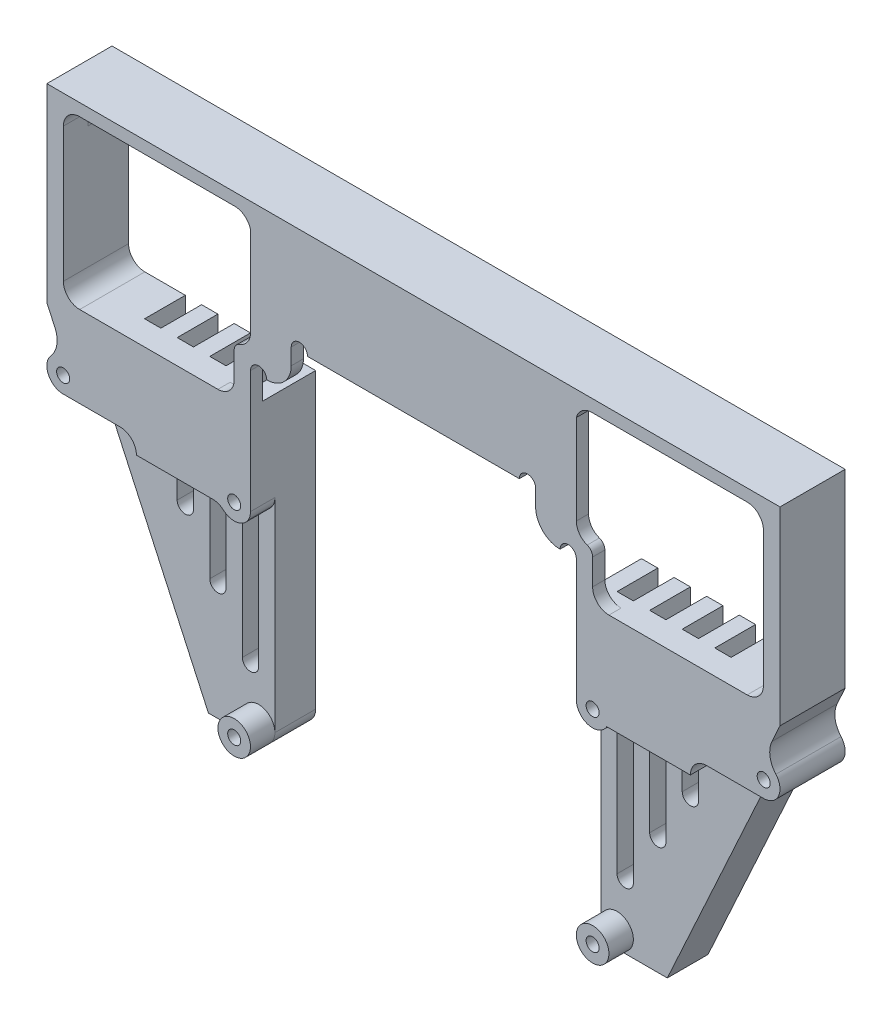
SolidWorks part; units mm, degrees
material "A2017"
ref_plane "正面" through (0, 0, 0) normal (0, 0, 1) x (1, 0, 0)
ref_plane "平面" through (0, 0, 0) normal (0, 1, 0) x (1, 0, 0)
ref_plane "右側面" through (0, 0, 0) normal (1, 0, 0) x (0, 0, -1)
sketch "ｽｹｯﾁ2" plane through (0, 0, 0) normal (0, 0, 1) x (1, 0, 0)
  line L0 (45, -77) -> (-45, -77)
  line L1 (-45, -77) -> (-45, -100.2724)
  line L2 (40.4547, -110.1895) -> (28.1283, -137.0833) construction
  line L3 (57.5, -85) -> (32.6737, -139.1665) construction
  line L4 (23.583, -145) -> (-23.583, -145) construction
  line L5 (-32.6737, -139.1665) -> (-57.5, -85) construction
  line L6 (45, -112.2727) -> (32.6737, -139.1665) construction
  line L7 (23.583, -145) -> (-23.583, -145) construction
  line L8 (-32.6737, -139.1665) -> (-45, -112.2727) construction
  line L9 (45, -77) -> (45, -100.2724)
  line L10 (45, -100.2724) -> (28.1665, -137)
  line L11 (-20, -80) -> (20, -80)
  line L12 (-28.1665, -137) -> (-45, -100.2724)
  line L13 (-28.1283, -137.0833) -> (-40.4547, -110.1895) construction
  line L15 (-20, -135) -> (-20, -80)
  line L19 (22, -137) -> (28.1665, -137)
  line L20 (-22, -137) -> (-28.1665, -137)
  line L22 (23.583, -140) -> (-23.583, -140) construction
  line L23 (20, -80) -> (20, -135.0066)
  line L24 (-43, -137) -> (-22, -137) construction
  line L25 (-20, -135) -> (-20, -79) construction
  line L26 (-45, -79) -> (-45, -135) construction
  line L27 (43, -77) -> (22, -77) construction
  line L28 (45, -135) -> (45, -79) construction
  line L29 (22, -137) -> (43, -137) construction
  line L30 (20, -79) -> (20, -135) construction
  arc A0 (23.583, -145) -> (32.6737, -139.1665) centre (23.583, -135) ccw construction
  arc A1 (-32.6737, -139.1665) -> (-23.583, -145) centre (-23.583, -135) ccw construction
  arc A2 (23.583, -145) -> (32.6737, -139.1665) centre (23.583, -135) ccw construction
  arc A3 (-32.6737, -139.1665) -> (-23.583, -145) centre (-23.583, -135) ccw construction
  arc A4 (-21.8257, -136.9924) -> (-20, -135) centre (-22, -135) ccw construction
  arc A5 (20.0076, -135.1743) -> (22, -137) centre (22, -135) ccw construction
  arc A8 (20, -135.0066) -> (22, -137) centre (22, -135) ccw
  arc A9 (-22, -137) -> (-20, -135) centre (-22, -135) ccw
  arc A10 (-28.1283, -137.0833) -> (-23.583, -140) centre (-23.583, -135) ccw construction
  arc A11 (23.583, -140) -> (28.1283, -137.0833) centre (23.583, -135) ccw construction
  dimension "D1" = 5
  dimension "D2" = 3
extrude "ﾎﾞｽ - 押し出し1" add sketch "ｽｹｯﾁ2" along normal blind 5
sketch "ｽｹｯﾁ3" plane through (0, 0, 5) normal (0, 0, 1) x (1, 0, 0)
  circle A0 centre (-43, -107) radius 2
  circle A1 centre (43, -107) radius 2
  circle A2 centre (43, -107) radius 1.25 construction
  dimension "D1" = 4
extrude "ﾎﾞｽ - 押し出し2" add sketch "ｽｹｯﾁ3" against normal up to surface (5 mm away) up to face at (0.0002, -111.1149, 0)
fillet "ﾌｨﾚｯﾄ1" radius 3 4 edges at (-42.8299, -105.0073, 2.5) (-41.3794, -108.172, 2.5) (41.3794, -108.172, 2.5) (42.8299, -105.0073, 2.5)
sketch "ｽｹｯﾁ4" plane through (0, 0, 5) normal (0, 0, 1) x (1, 0, 0)
  circle A0 centre (-43, -107) radius 2
  circle A1 centre (-22, -110) radius 2
  circle A2 centre (-22, -135) radius 2
  circle A3 centre (22, -135) radius 2
  circle A4 centre (22, -110) radius 2
  circle A5 centre (43, -107) radius 2
  dimension "D1" = 4
extrude "ﾎﾞｽ - 押し出し3" add sketch "ｽｹｯﾁ4" along normal blind 3
sketch "ｽｹｯﾁ5" plane through (0, 0, 5) normal (0, 0, 1) x (1, 0, 0)
  line L0 (20, -80) -> (20, -110) construction
  line L1 (20, -98.9998) -> (42.9701, -98.9998)
  line L2 (20, -98.9998) -> (20, -108.9998)
  line L3 (34, -108.9998) -> (42.9701, -108.9998)
  line L4 (42.9701, -98.9998) -> (42.9701, -108.9998)
  line L5 (20, -110) -> (20, -135) construction
  line L6 (20, -110.9998) -> (34, -110.9998)
  line L7 (20, -110.9998) -> (20, -108.9998)
  line L8 (0, -77) -> (0, -134.0805) construction
  line L9 (34, -110.9998) -> (34, -108.9998)
  line L10 (45, -77) -> (-45, -77) construction
  line L11 (-34, -110.9998) -> (-34, -108.9998)
  line L12 (-20, -110.9998) -> (-20, -108.9998)
  line L13 (-20, -110.9998) -> (-34, -110.9998)
  line L14 (-42.9701, -98.9998) -> (-42.9701, -108.9998)
  line L15 (-34, -108.9998) -> (-42.9701, -108.9998)
  line L16 (-20, -98.9998) -> (-20, -108.9998)
  line L17 (-20, -98.9998) -> (-42.9701, -98.9998)
  circle A0 centre (43, -107) radius 2 construction
  arc A1 (42.9701, -108.9998) -> (40.198, -110.7495) centre (42.9252, -111.9994) ccw construction
  dimension "D1" = 10
  dimension "D2" = 14
  dimension "D3" = 2
extrude "ﾎﾞｽ - 押し出し4" add sketch "ｽｹｯﾁ5" along normal up to surface (3 mm away) up to face at (24, -110, 8)
sketch "ｽｹｯﾁ6" plane through (0, 0, 8) normal (0, 0, 1) x (1, 0, 0)
  line L0 (0, -77) -> (0, -111.4657) construction
  line L1 (42.9701, -98.9998) -> (37.9701, -98.9998)
  line L2 (42.9701, -98.9998) -> (42.9701, -103.9998)
  line L3 (42.9701, -103.9998) -> (37.9701, -103.9998)
  line L4 (37.9701, -98.9998) -> (37.9701, -103.9998)
  line L5 (45, -77) -> (-45, -77) construction
  line L6 (-37.9701, -98.9998) -> (-37.9701, -103.9998)
  line L7 (-42.9701, -103.9998) -> (-37.9701, -103.9998)
  line L8 (-42.9701, -98.9998) -> (-42.9701, -103.9998)
  line L9 (-42.9701, -98.9998) -> (-37.9701, -98.9998)
  dimension "D1" = 5
  dimension "D2" = 5
extrude "ｶｯﾄ - 押し出し1" cut sketch "ｽｹｯﾁ6" against normal up to surface (3 mm away) up to face at (20.3913, -135.9447, 5)
sketch "ｽｹｯﾁ7" plane through (0, 0, 5) normal (0, 0, 1) x (1, 0, 0)
  line L0 (45, -100.2724) -> (45, -77) construction
  line L1 (44.0112, -102.4297) -> (45, -100.2724) construction
  line L2 (45, -100.2724) -> (45, -77)
  line L3 (44.0112, -102.4297) -> (45, -100.2724)
  line L4 (-45, -77) -> (-45, -100.2724) construction
  line L5 (-45, -100.2724) -> (-44.0112, -102.4297) construction
  line L6 (-45, -77) -> (-45, -100.2724)
  line L7 (-45, -100.2724) -> (-44.0112, -102.4297)
  line L8 (45, -77) -> (-45, -77) construction
  line L9 (45, -77) -> (-45, -77)
  line L10 (42.9701, -105.0002) -> (42.9701, -80)
  line L11 (42.9701, -80) -> (-42.9701, -80)
  line L12 (-42.9701, -80) -> (-42.9701, -105.0002)
  arc A0 (44.0112, -102.4297) -> (44.4954, -105.6719) centre (46.7384, -103.6797) ccw construction
  arc A1 (44.0112, -102.4297) -> (44.4954, -105.6719) centre (46.7384, -103.6797) ccw
  arc A2 (-44.4954, -105.6719) -> (-44.0112, -102.4297) centre (-46.7384, -103.6797) ccw construction
  arc A3 (-44.4954, -105.6719) -> (-44.0112, -102.4297) centre (-46.7384, -103.6797) ccw
  arc A5 (42.9701, -108.9998) -> (42.9701, -105.0002) centre (43, -107) ccw construction
  arc A6 (-42.9701, -105.0002) -> (-44.4954, -105.6719) centre (-43, -107) ccw construction
  arc A8 (44.4954, -105.6719) -> (42.9701, -105.0002) centre (43, -107) ccw
  arc A9 (-42.9701, -105.0002) -> (-44.4954, -105.6719) centre (-43, -107) ccw
extrude "ﾎﾞｽ - 押し出し5" add sketch "ｽｹｯﾁ7" along normal up to surface (3 mm away) up to face at (32.6255, -106.7271, 8)
sketch "ｽｹｯﾁ8" plane through (0, 0, 5) normal (0, 0, 1) x (1, 0, 0)
  line L0 (42.9701, -103.9998) -> (42.9701, -80) construction
  line L1 (42.9701, -80) -> (20, -80) construction
  line L2 (20, -80) -> (20, -98.9998) construction
  line L3 (20, -98.9998) -> (37.9701, -98.9998) construction
  line L4 (37.9701, -98.9998) -> (37.9701, -103.9998) construction
  line L5 (37.9701, -103.9998) -> (42.9701, -103.9998) construction
  line L6 (-20, -80) -> (-42.9701, -80) construction
  line L7 (-42.9701, -80) -> (-42.9701, -103.9998) construction
  line L8 (-42.9701, -103.9998) -> (-37.9701, -103.9998) construction
  line L9 (-37.9701, -103.9998) -> (-37.9701, -98.9998) construction
  line L10 (-37.9701, -98.9998) -> (-20, -98.9998) construction
  line L11 (-20, -98.9998) -> (-20, -80) construction
  line L12 (42.9701, -103.9998) -> (42.9701, -80)
  line L13 (42.9701, -80) -> (20, -80)
  line L14 (20, -80) -> (20, -98.9998)
  line L15 (20, -98.9998) -> (37.9701, -98.9998)
  line L16 (37.9701, -98.9998) -> (37.9701, -103.9998)
  line L17 (37.9701, -103.9998) -> (42.9701, -103.9998)
  line L18 (-20, -80) -> (-42.9701, -80)
  line L19 (-42.9701, -80) -> (-42.9701, -103.9998)
  line L20 (-42.9701, -103.9998) -> (-37.9701, -103.9998)
  line L21 (-37.9701, -103.9998) -> (-37.9701, -98.9998)
  line L22 (-37.9701, -98.9998) -> (-20, -98.9998)
  line L23 (-20, -98.9998) -> (-20, -80)
extrude "ｶｯﾄ - 押し出し2" cut sketch "ｽｹｯﾁ8" against normal through all
fillet "ﾌｨﾚｯﾄ2" radius 2 6 edges at (-42.9701, -103.9998, 4) (-37.9701, -103.9998, 4) (37.9701, -103.9998, 4) (42.9701, -103.9998, 4) (42.9701, -80, 4) (-42.9701, -80, 4)
sketch "ｽｹｯﾁ9" plane through (0, 0, 8) normal (0, 0, 1) x (1, 0, 0)
  line L0 (20, -77) -> (20, -82.5) construction
  line L1 (42.9701, -82) -> (20, -82)
  line L2 (42.9701, -82) -> (42.9701, -78.5)
  line L3 (42.9701, -78.5) -> (20, -78.5)
  line L4 (20, -82) -> (20, -78.5)
  line L5 (45, -77) -> (-45, -77) construction
  line L6 (0, -77) -> (0, -137.6393) construction
  line L7 (-20, -82) -> (-20, -78.5)
  line L8 (-42.9701, -78.5) -> (-20, -78.5)
  line L9 (-42.9701, -82) -> (-42.9701, -78.5)
  line L10 (-42.9701, -82) -> (-20, -82)
  dimension "D1" = 1.5
extrude "ｶｯﾄ - 押し出し3" cut sketch "ｽｹｯﾁ9" against normal blind 3
fillet "ﾌｨﾚｯﾄ3" radius 2 4 edges at (42.9701, -78.5, 6.5) (20, -78.5, 6.5) (-20, -78.5, 6.5) (-42.9701, -78.5, 6.5)
fillet "ﾌｨﾚｯﾄ4" radius 2 5 edges at (34, -108.9998, 6.5) (-20, -110.9998, 6.5) (20, -110.9998, 6.5) (-23.7322, -110.9998, 6.5) (-34, -108.9998, 6.5)
sketch "ｽｹｯﾁ10" plane through (0, 0, 0) normal (0, 0, -1) x (-1, 0, 0)
  line L0 (-23, -98.9998) -> (-23, -128.9998) construction
  line L1 (-20, -98.9998) -> (-37.9701, -98.9998) construction
  line L2 (-22, -98.9998) -> (-22, -128.9998)
  line L3 (-24, -98.9998) -> (-24, -128.9998)
  line L4 (-20, -98.9998) -> (-20, -135.0066) construction
  line L5 (-27, -98.9998) -> (-27, -122.6356) construction
  line L6 (-26, -98.9998) -> (-26, -122.6356)
  line L7 (-28, -98.9998) -> (-28, -122.6356)
  line L8 (-23, -128.9998) -> (-39.9701, -101.9998) construction
  line L9 (-31, -98.9998) -> (-31, -116.2715) construction
  line L10 (-30, -98.9998) -> (-30, -116.2715)
  line L11 (-32, -98.9998) -> (-32, -116.2715)
  line L12 (-35, -98.9998) -> (-35, -109.9073) construction
  line L13 (-34, -98.9998) -> (-34, -109.9073)
  line L14 (-36, -98.9998) -> (-36, -109.9073)
  line L15 (0, -77) -> (0, -136.588) construction
  line L16 (-45, -77) -> (45, -77) construction
  line L17 (23, -98.9998) -> (23, -128.9998) construction
  line L18 (22, -98.9998) -> (22, -128.9998)
  line L19 (24, -98.9998) -> (24, -128.9998)
  line L20 (27, -98.9998) -> (27, -122.6356) construction
  line L21 (26, -98.9998) -> (26, -122.6356)
  line L22 (28, -98.9998) -> (28, -122.6356)
  line L23 (31, -98.9998) -> (31, -116.2715) construction
  line L24 (30, -98.9998) -> (30, -116.2715)
  line L25 (32, -98.9998) -> (32, -116.2715)
  line L26 (35, -98.9998) -> (35, -109.9073) construction
  line L27 (34, -98.9998) -> (34, -109.9073)
  line L28 (36, -98.9998) -> (36, -109.9073)
  line L29 (23, -128.9998) -> (39.9701, -101.9998) construction
  arc A0 (-22, -98.9998) -> (-24, -98.9998) centre (-23, -98.9998) ccw
  arc A1 (-24, -128.9998) -> (-22, -128.9998) centre (-23, -128.9998) ccw
  arc A2 (-26, -98.9998) -> (-28, -98.9998) centre (-27, -98.9998) ccw
  arc A3 (-28, -122.6356) -> (-26, -122.6356) centre (-27, -122.6356) ccw
  arc A4 (-30, -98.9998) -> (-32, -98.9998) centre (-31, -98.9998) ccw
  arc A5 (-32, -116.2715) -> (-30, -116.2715) centre (-31, -116.2715) ccw
  arc A6 (-34, -98.9998) -> (-36, -98.9998) centre (-35, -98.9998) ccw
  arc A7 (-36, -109.9073) -> (-34, -109.9073) centre (-35, -109.9073) ccw
  arc A8 (22, -98.9998) -> (24, -98.9998) centre (23, -98.9998) cw
  arc A9 (24, -128.9998) -> (22, -128.9998) centre (23, -128.9998) cw
  arc A10 (26, -98.9998) -> (28, -98.9998) centre (27, -98.9998) cw
  arc A11 (28, -122.6356) -> (26, -122.6356) centre (27, -122.6356) cw
  arc A12 (30, -98.9998) -> (32, -98.9998) centre (31, -98.9998) cw
  arc A13 (32, -116.2715) -> (30, -116.2715) centre (31, -116.2715) cw
  arc A14 (34, -98.9998) -> (36, -98.9998) centre (35, -98.9998) cw
  arc A15 (36, -109.9073) -> (34, -109.9073) centre (35, -109.9073) cw
  point P4 (-23, -113.9998)
  point P13 (-27, -110.8177)
  point P23 (-31, -107.6356)
  point P30 (-35, -104.4536)
  point P42 (23, -113.9998)
  point P49 (27, -110.8177)
  point P56 (31, -107.6356)
  point P63 (35, -104.4536)
  dimension "D1" = 2
  dimension "D2" = 2
  dimension "D3" = 30
  dimension "D4" = 2
  dimension "D5" = 2
  dimension "D6" = 2
extrude "ｶｯﾄ - 押し出し4" cut sketch "ｽｹｯﾁ10" against normal blind 5
hole_wizard "M2 ねじ穴1" positions "ｽｹｯﾁ11" profile "ｽｹｯﾁ13" tap size "M2" standard "JIS" end condition through all
sketch "ｽｹｯﾁ11" plane through (0, 0, 8) normal (0, 0, 1) x (1, 0, 0)
  point P0 (43, -107)
  point P3 (22, -110)
  point P6 (22, -135)
  point P9 (-22, -110)
  point P12 (-22, -135)
  point P15 (-43, -107)
sketch "ｽｹｯﾁ13" plane through (43, -107, 8) normal (1, 0, 0) x (0, -1, 0)
  line L0 (0, 0) -> (0, 8)
  line L1 (0, 8) -> (0.8, 8)
  line L2 (0.8, 8) -> (0.8, 0)
  line L5 (0.8, 0) -> (0, 0)
  line L11 (0, -6.35) -> (0, 107.95) construction
  dimension "次ｻｰﾌｪｽまでのねじ下穴ﾄﾞﾘﾙ直径" = 1.6
  dimension "次ｻｰﾌｪｽまでのねじ下穴ﾄﾞﾘﾙの深さ" = 8
cosmetic thread "穴のねじ山1" parameters "D2"=2
cosmetic thread "穴のねじ山2" parameters "D2"=2
cosmetic thread "穴のねじ山3" parameters "D2"=2
cosmetic thread "穴のねじ山4" parameters "D2"=2
cosmetic thread "穴のねじ山5" parameters "D2"=2
cosmetic thread "穴のねじ山6" parameters "D2"=2
sketch "ｽｹｯﾁ14" plane through (0, 0, 8) normal (0, 0, 1) x (1, 0, 0)
  line L0 (-42.9701, -101.9998) -> (-42.9701, -80.5) construction
  line L1 (-40.9701, -103.9998) -> (-39.9701, -103.9998) construction
  line L2 (-37.9701, -101.9998) -> (-37.9701, -98.9998) construction
  line L3 (42.9701, -80.5) -> (42.9701, -101.9998) construction
  line L4 (39.9701, -103.9998) -> (40.9701, -103.9998) construction
  line L5 (37.9701, -98.9998) -> (37.9701, -101.9998) construction
  line L6 (-42.9701, -101.9998) -> (-42.9701, -98.9998)
  line L7 (-40.9701, -103.9998) -> (-39.9701, -103.9998)
  line L8 (-37.9701, -101.9998) -> (-37.9701, -98.9998)
  line L9 (42.9701, -98.9998) -> (42.9701, -101.9998)
  line L10 (39.9701, -103.9998) -> (40.9701, -103.9998)
  line L11 (37.9701, -98.9998) -> (37.9701, -101.9998)
  line L12 (37.9701, -98.9998) -> (42.9701, -98.9998)
  line L13 (-37.9701, -98.9998) -> (-42.9701, -98.9998)
  arc A0 (-42.9701, -101.9998) -> (-40.9701, -103.9998) centre (-40.9701, -101.9998) ccw construction
  arc A1 (-39.9701, -103.9998) -> (-37.9701, -101.9998) centre (-39.9701, -101.9998) ccw construction
  arc A2 (40.9701, -103.9998) -> (42.9701, -101.9998) centre (40.9701, -101.9998) ccw construction
  arc A3 (37.9701, -101.9998) -> (39.9701, -103.9998) centre (39.9701, -101.9998) ccw construction
  arc A4 (-42.9701, -101.9998) -> (-40.9701, -103.9998) centre (-40.9701, -101.9998) ccw
  arc A5 (-39.9701, -103.9998) -> (-37.9701, -101.9998) centre (-39.9701, -101.9998) ccw
  arc A6 (40.9701, -103.9998) -> (42.9701, -101.9998) centre (40.9701, -101.9998) ccw
  arc A7 (37.9701, -101.9998) -> (39.9701, -103.9998) centre (39.9701, -101.9998) ccw
extrude "ﾎﾞｽ - 押し出し6" add sketch "ｽｹｯﾁ14" against normal up to surface (8 mm away) up to face at (43.8, -107, 0)
fillet "ﾌｨﾚｯﾄ5" radius 2 2 edges at (-42.9701, -98.9998, 4) (42.9701, -98.9998, 4)
sketch "ｽｹｯﾁ15" plane through (0, 0, 8) normal (0, 0, 1) x (1, 0, 0)
  line L0 (-14.5, -90) -> (14.5, -90) construction
  line L1 (-20, -80) -> (20, -80)
  line L2 (-20, -80) -> (-20, -90)
  line L3 (-20, -90) -> (20, -90)
  line L4 (20, -80) -> (20, -90)
extrude "ﾎﾞｽ - 押し出し8" add sketch "ｽｹｯﾁ15" against normal blind 1.5
sketch "ｽｹｯﾁ16" plane through (0, 0, 8) normal (0, 0, 1) x (1, 0, 0)
  line L2 (20, -98.9998) -> (20, -95)
  line L3 (20, -95.5) -> (20, -93) construction
  line L4 (20, -95) -> (18, -95)
  line L5 (15, -92) -> (15, -90)
  line L6 (-20, -90) -> (20, -90) construction
  line L11 (20, -135) -> (20, -79) construction
  line L12 (20, -98.9998) -> (22, -98.9998) construction
  line L13 (20, -98.9998) -> (22, -98.9998)
  line L14 (22, -98.9998) -> (22, -93)
  line L15 (15, -90) -> (20, -90)
  line L16 (22, -93) -> (20, -93)
  line L17 (20, -93) -> (20, -90)
  arc A0 (15, -92) -> (18, -95) centre (18, -92) ccw construction
  arc A1 (15, -92) -> (18, -95) centre (18, -92) ccw
  dimension "D1" = 3
extrude "ﾎﾞｽ - 押し出し9" add sketch "ｽｹｯﾁ16" against normal up to surface (1.5 mm away) up to face at (0, -85, 6.5)
mirror "ﾐﾗｰ1" about plane through (0, 0, 0) normal (1, 0, 0) of "ﾎﾞｽ - 押し出し9"
fillet "ﾌｨﾚｯﾄ7" radius 2 2 edges at (-20, -93, 7.25) (20, -93, 7.25)
fillet "ﾌｨﾚｯﾄ8" radius 1 2 edges at (22, -93, 7.25) (-22, -93, 7.25)
fillet "ﾌｨﾚｯﾄ9" radius 2 2 edges at (22, -98.9998, 7.25) (-22, -98.9998, 7.25)
sketch "ｽｹｯﾁ17" plane through (0, 0, 8) normal (0, 0, 1) x (1, 0, 0)
  line L0 (-18, -95) -> (-20, -95) construction
  line L1 (-15, -90) -> (15, -90) construction
  line L2 (0, -77) -> (0, -99.7898) construction
  line L3 (45, -77) -> (-45, -77) construction
  circle A0 centre (-19, -95) radius 1
  circle A1 centre (-14, -90) radius 1
  circle A2 centre (14, -90) radius 1
  circle A3 centre (19, -95) radius 1
  dimension "D1" = 2
extrude "ｶｯﾄ - 押し出し5" cut sketch "ｽｹｯﾁ17" against normal through all
